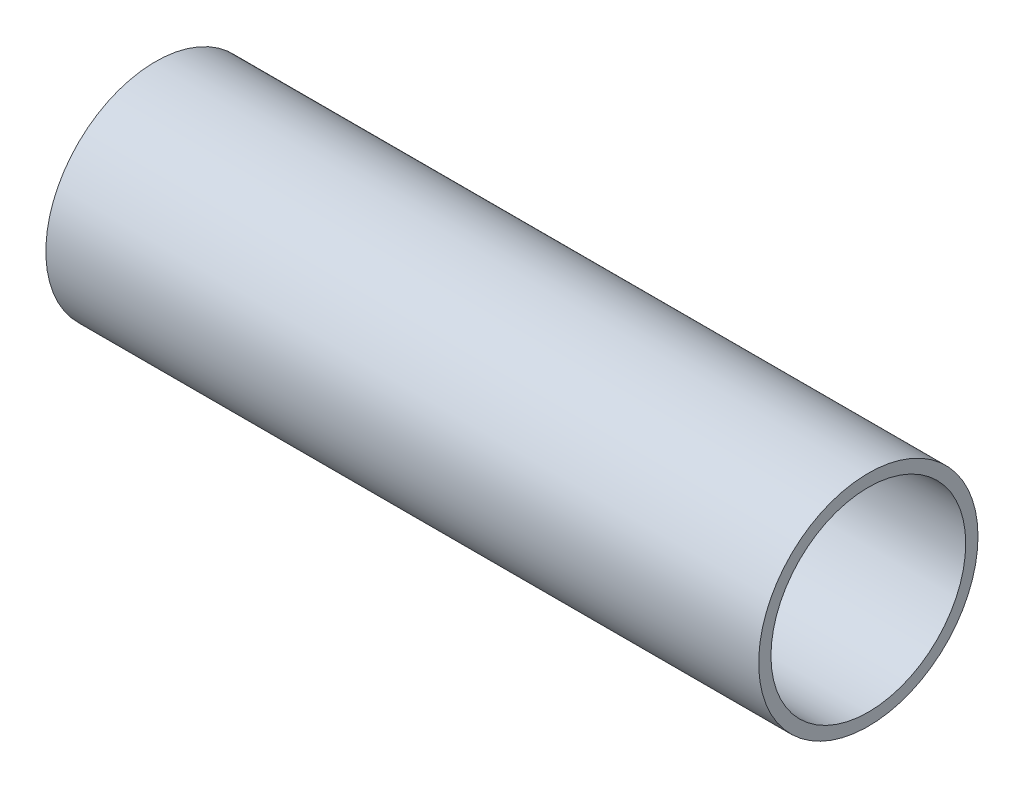
SolidWorks part; units mm, degrees
ref_plane "Front Plane" through (0, 0, 0) normal (0, 0, 1) x (1, 0, 0)
ref_plane "Top Plane" through (0, 0, 0) normal (0, 1, 0) x (1, 0, 0)
ref_plane "Right Plane" through (0, 0, 0) normal (1, 0, 0) x (0, 0, -1)
sketch "Sketch1" plane through (0, 0, 0) normal (1, 0, 0) x (0, 0, -1)
  circle A0 centre (0, 0) radius 6.35
  circle A1 centre (0, 0) radius 5.6388
  dimension "D1" = 12.7
  dimension "D2" = 11.2776
extrude "Boss-Extrude1" add sketch "Sketch1" along normal blind 41.275
equation "\"D1@Boss-Extrude1\"=(1+3/8+1/8+2*1/16)"
